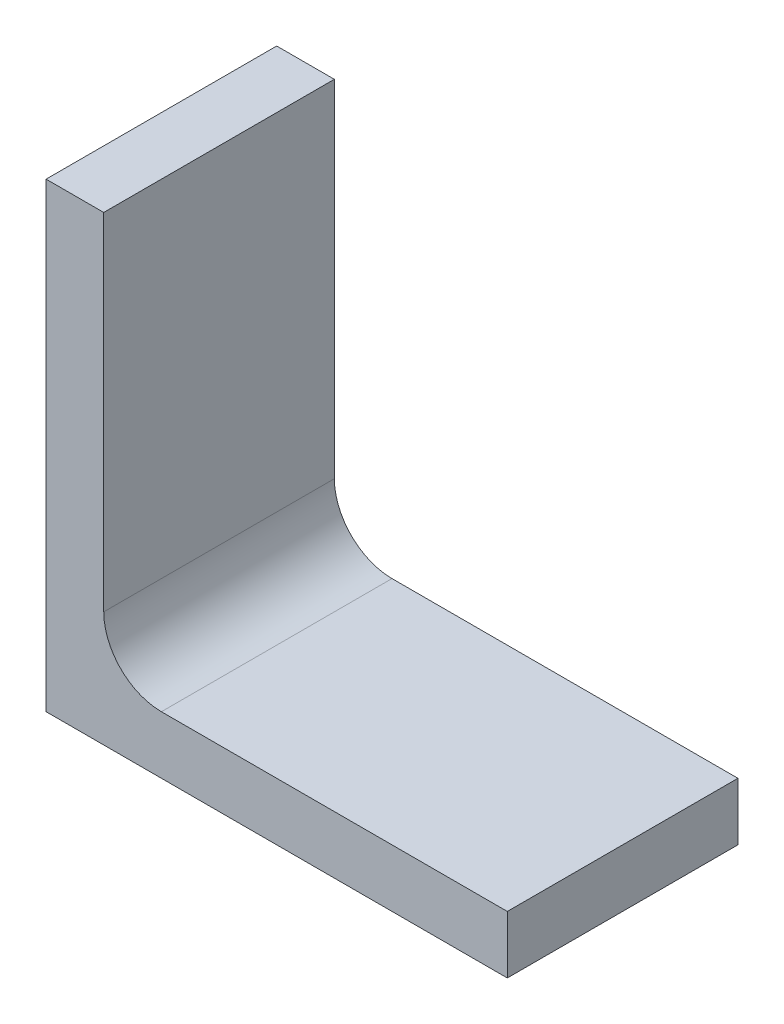
SolidWorks part; units mm, degrees
ref_plane "Plane1" through (0, 0, 0) normal (0, 0, 1) x (1, 0, 0)
ref_plane "Plane2" through (0, 0, 0) normal (0, 1, 0) x (1, 0, 0)
ref_plane "Plane3" through (0, 0, 0) normal (1, 0, 0) x (0, 0, -1)
sketch "Sketch1" plane through (0, 0, 0) normal (0, 0, 1) x (1, 0, 0)
  line L0 (0, 0) -> (0, 50.8)
  line L1 (0, 50.8) -> (12.7, 50.8) construction
  line L2 (6.35, 50.8) -> (6.35, 12.7)
  line L3 (12.7, 6.35) -> (50.8, 6.35)
  line L4 (50.8, 12.7) -> (50.8, 0) construction
  line L5 (50.8, 0) -> (0, 0)
  line L6 (0, 50.8) -> (6.35, 50.8)
  line L7 (50.8, 0) -> (50.8, 6.35)
  arc A2 (12.7, 6.35) -> (6.35, 12.7) centre (12.7, 12.7) cw
  dimension "D1" = 6.35
  dimension "V_leg" = 50.8
  dimension "H_leg" = 50.8
extrude "BaseAnglese" add sketch "Sketch1" along normal mid plane 25.4
equation "\"D1@Sketch1\" = \"Thickness@Sketch1\""
